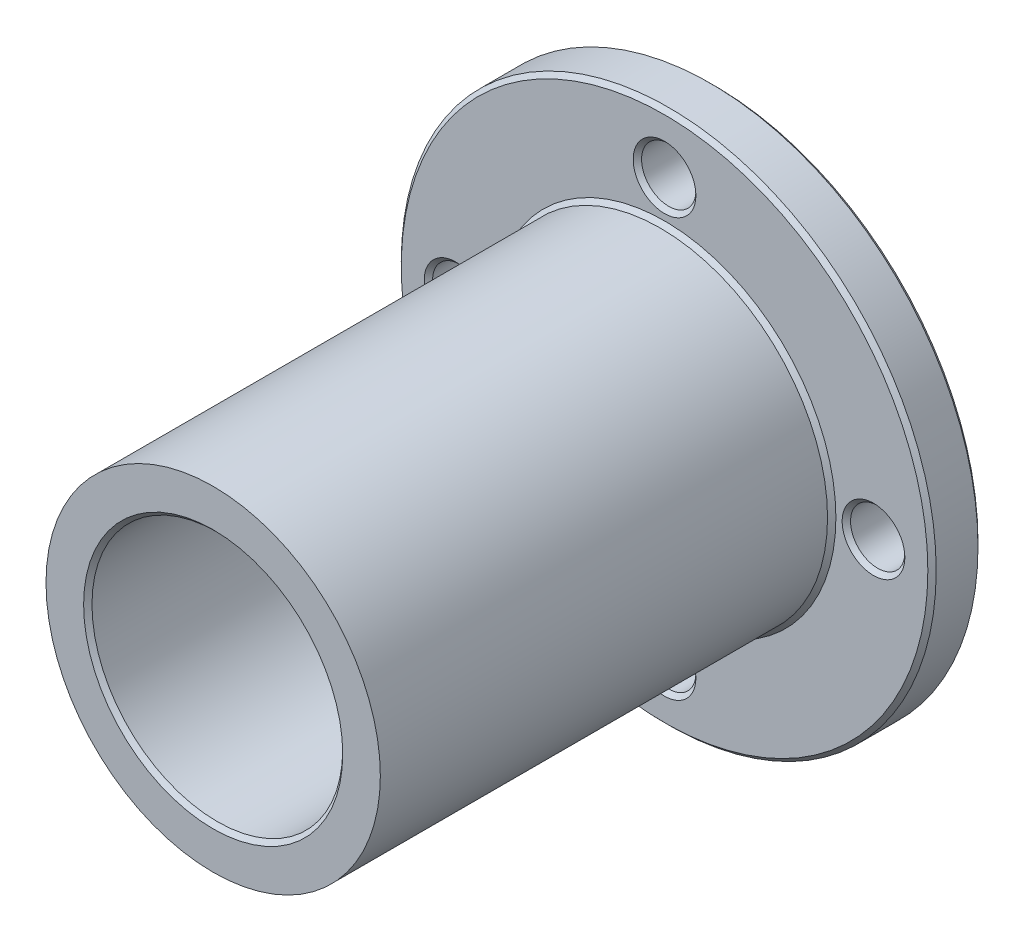
SolidWorks part; units mm, degrees
ref_plane "Front Plane" through (0, 0, 0) normal (0, 0, 1) x (1, 0, 0)
ref_plane "Top Plane" through (0, 0, 0) normal (0, 1, 0) x (1, 0, 0)
ref_plane "Right Plane" through (0, 0, 0) normal (1, 0, 0) x (0, 0, -1)
sketch "Sketch1" plane through (0, 0, 0) normal (0, 0, 1) x (1, 0, 0)
  circle A0 centre (0, 0) radius 32
  circle A1 centre (0, 0) radius 20
  dimension "D1" = 64
  dimension "D2" = 40
extrude "Boss-Extrude1" add sketch "Sketch1" along normal blind 6
extrude "Boss-Extrude2" add sketch "Sketch1<2>" along normal blind 60 contours A1 region at (0, 0, 0)
sketch "Sketch1<2>" plane through (0, 0, 0) normal (0, 0, 1) x (1, 0, 0) same geometry as "Sketch1"
hole_wizard "CBORE for M6 Hex Head Bolt1" positions "Sketch5" profile "Sketch6" counterbore size "M6" standard "ISO" end condition through all
sketch "Sketch5" plane through (0, 0, 0) normal (0, 0, -1) x (-1, 0, 0)
  point P0 (0, 0)
sketch "Sketch6" plane through (0, 0, 0) normal (1, 0, 0) x (0, 1, 0)
  line L0 (0, 0) -> (0, 60)
  line L1 (0, 60) -> (15, 60)
  line L3 (15, 60) -> (15, 2.3)
  line L4 (15, 2.3) -> (20, 2.3)
  line L5 (20, 2.3) -> (20, 0)
  line L7 (20, 0) -> (0, 0)
  line L11 (0, -6.35) -> (0, 107.95) construction
  dimension "Thru Hole Dia." = 30
  dimension "Thru Hole Depth" = 60
  dimension "C'Bore Dia." = 40
  dimension "C'Bore Depth" = 2.3
sketch "Sketch7" plane through (0, 0, 0) normal (0, 0, -1) x (-1, 0, 0)
  circle A0 centre (0, 0) radius 25 construction
  circle A1 centre (0, 25) radius 3.25
  circle A2 centre (25, 0) radius 3.25
  circle A3 centre (0, -25) radius 3.25
  circle A4 centre (-25, 0) radius 3.25
  point P14 (0, 0)
  dimension "D1" = 50
  dimension "D2" = 6.5
  dimension "D3" = 4
extrude "Cut-Extrude1" cut sketch "Sketch7" against normal blind 6
chamfer "Chamfer1" distance 0.5 angle 45 13 edges at (32, 0, 0) (-20, 0, 0) (21.75, 0, 0) (-3.25, -25, 0) (-28.25, 0, 0) (-3.25, 25, 0) (20, 0, 6) (32, 0, 6) (21.75, 0, 6) (-3.25, -25, 6) (-28.25, 0, 6) (-3.25, 25, 6) (-15, 0, 60)
